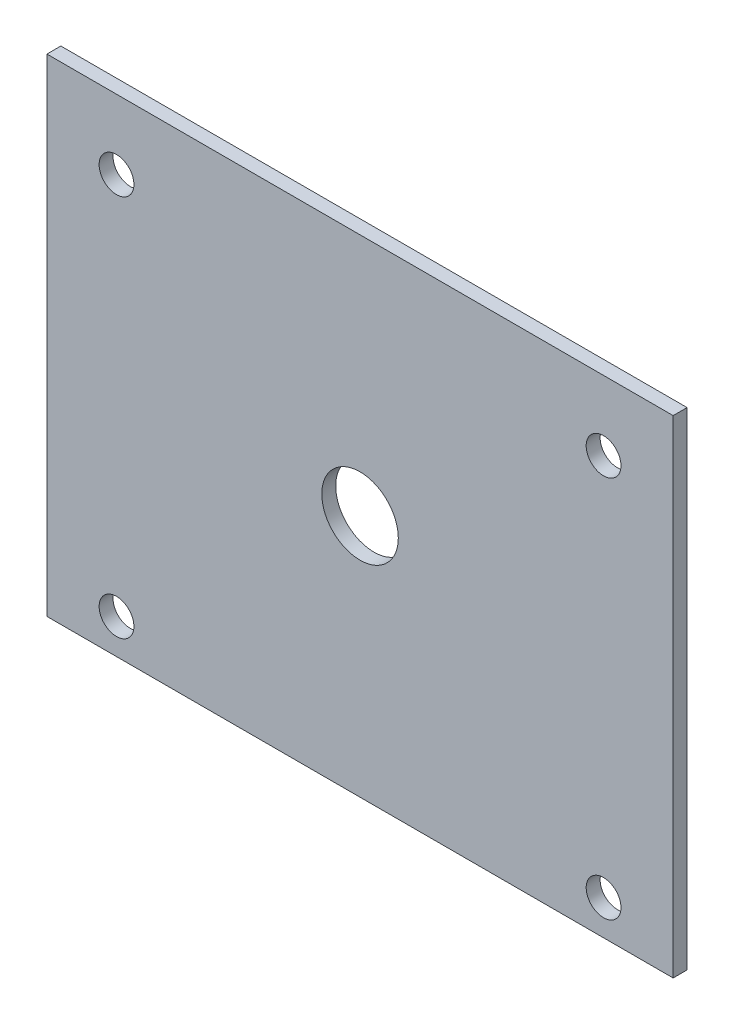
SolidWorks part; units mm, degrees
ref_plane "Спереди" through (0, 0, 0) normal (0, 0, 1) x (1, 0, 0)
ref_plane "Сверху" through (0, 0, 0) normal (0, 1, 0) x (1, 0, 0)
ref_plane "Справа" through (0, 0, 0) normal (1, 0, 0) x (0, 0, -1)
sketch "Эскиз1" plane through (0, 0, 0) normal (0, 0, 1) x (1, 0, 0)
  line L0 (0, 35) -> (90, 35) construction
  line L1 (0, 0) -> (90, 0)
  line L2 (0, 0) -> (0, 70)
  line L3 (0, 70) -> (90, 70)
  line L4 (90, 0) -> (90, 70)
  line L6 (0, 60) -> (90, 60) construction
  line L8 (0, 5) -> (90, 5) construction
  line L10 (80, 60) -> (80, 5) construction
  line L12 (10, 60) -> (10, 5) construction
  circle A0 centre (45, 35) radius 5.5
  circle A1 centre (10, 60) radius 2.5
  circle A3 centre (80, 60) radius 2.5
  circle A4 centre (10, 5) radius 2.5
  circle A5 centre (80, 5) radius 2.5
  point P18 (10, 5)
  dimension "D2" = 11
  dimension "D3" = 5
  dimension "D1" = 70
  dimension "D4" = 10
  dimension "D5" = 10
  dimension "D6" = 10
  dimension "D7" = 10
  dimension "D8" = 90
base flange "Базовая кромка1" sketch "Эскиз1" thickness 2 reverse thickness direction no parameters "D1"=0.7366
sketch "Сгиб-Линии1" plane through (0, 0, 0) normal (0, 1, 0) x (1, 0, 0)
sketch "Граничная рамка1" plane through (0, 0, 0) normal (0, 1, 0) x (1, 0, 0)
sheet metal parameters "Листовой металл3" thickness 2 parameters "D1"=0.7366
flat pattern "Развертка3" [suppressed]
sketch "Сгиб-Линии2" plane through (0, 0, 0) normal (0, 1, 0) x (1, 0, 0)
sketch "Граничная рамка2" [suppressed] plane through (0, 0, 0) normal (0, 1, 0) x (1, 0, 0)
